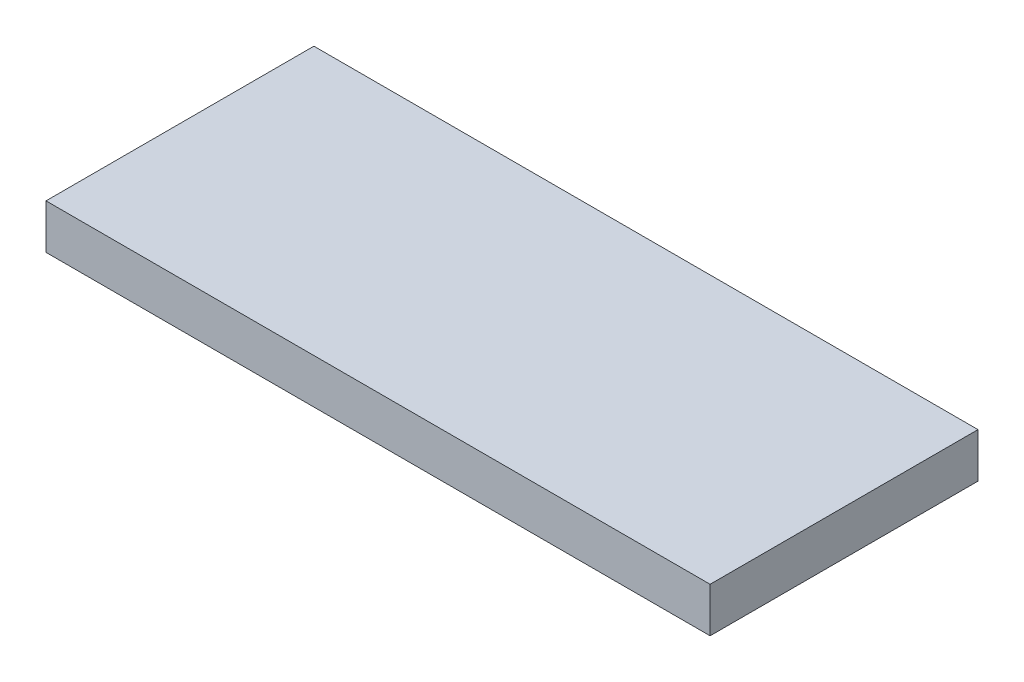
SolidWorks part; units mm, degrees
ref_plane "Front Plane" through (0, 0, 0) normal (0, 0, 1) x (1, 0, 0)
ref_plane "Top Plane" through (0, 0, 0) normal (0, 1, 0) x (1, 0, 0)
ref_plane "Right Plane" through (0, 0, 0) normal (1, 0, 0) x (0, 0, -1)
sketch "Sketch1" plane through (0, 0, 0) normal (0, 0, 1) x (1, 0, 0)
  line L0 (0, 0) -> (0, 76.2)
  line L5 (0, 76.2) -> (88.098, 76.2)
  line L6 (88.098, 76.2) -> (88.098, 101.6)
  line L7 (0, 0) -> (6.35, 0)
  line L8 (6.35, 0) -> (6.35, 76.2)
  line L9 (6.35, 76.2) -> (6.35, 69.85)
  line L10 (6.35, 69.85) -> (101.1141, 69.85)
  line L11 (88.098, 101.6) -> (94.448, 101.6)
  line L12 (94.448, 101.6) -> (94.448, 69.85)
  dimension "D1" = 25.4
  dimension "D2" = 76.2
extrude "Boss-Extrude1" add sketch "Sketch1" along normal blind 38.1 contours L7 L8 L5 L0 | L12 L11 L6 L5 L8 L10 region at (3.175, 38.1, 0) region at (47.224, 75.2636, 0)
sketch "Sketch2" plane through (0, 0, 0) normal (-1, 0, 0) x (0, 0, 1)
  line L0 (19.05, 20.32) -> (19.05, 42.672)
  line L1 (0, 0) -> (0, 76.2) construction
  line L2 (38.1, 0) -> (0, 0)
  line L3 (38.1, 0) -> (38.1, 50.8)
  line L4 (38.1, 50.8) -> (0, 50.8)
  line L5 (0, 0) -> (0, 50.8)
  line L6 (38.1, 0) -> (38.1, 20.32)
  line L7 (38.1, 20.32) -> (0, 20.32)
  circle A0 centre (19.05, 20.32) radius 11.049
  circle A1 centre (19.05, 42.672) radius 3.556
  dimension "D1" = 22.352
  dimension "D2" = 20.32
extrude "Cut-Extrude1" cut sketch "Sketch2" against normal blind 6.35 contours A0
extrude "Cut-Extrude2" cut sketch "Sketch2<4>" against normal blind 6.35 contours A1
sketch "Sketch2<4>" plane through (0, 0, 0) normal (-1, 0, 0) x (0, 0, 1) same geometry as "Sketch2"
sketch "Sketch4" plane through (0, 0, 38.1) normal (0, 0, 1) x (1, 0, 0)
  line L5 (88.098, 76.2) -> (102.3424, 76.2)
  line L6 (88.098, 76.2) -> (88.098, 112.6724)
  line L7 (88.098, 112.6724) -> (102.3424, 112.6724)
  line L8 (102.3424, 76.2) -> (102.3424, 112.6724)
  line L9 (6.35, 69.85) -> (-28.4909, 69.85)
  line L10 (6.35, 69.85) -> (6.35, -10.2972)
  line L11 (6.35, -10.2972) -> (-28.4909, -10.2972)
  line L12 (-28.4909, 69.85) -> (-28.4909, -10.2972)
extrude "Cut-Extrude4" cut sketch "Sketch4" against normal blind 76.2
sketch "Sketch5" plane through (0, 69.85, 0) normal (0, -1, 0) x (1, 0, 0)
  line L0 (0, 0) -> (94.448, 0) construction
  line L1 (0, 38.1) -> (6.35, 38.1)
  line L2 (0, 38.1) -> (0, 0)
  line L3 (0, 0) -> (6.35, 0)
  line L4 (6.35, 38.1) -> (6.35, 0)
